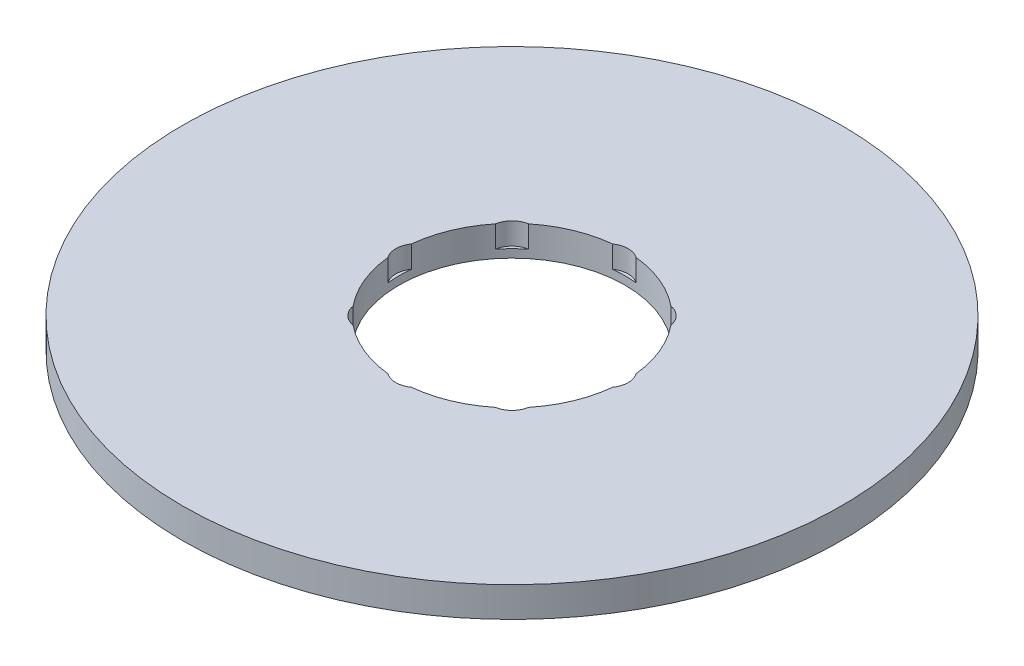
SolidWorks part; units mm, degrees
ref_plane "Front Plane" through (0, 0, 0) normal (0, 0, 1) x (1, 0, 0)
ref_plane "Top Plane" through (0, 0, 0) normal (0, 1, 0) x (1, 0, 0)
ref_plane "Right Plane" through (0, 0, 0) normal (1, 0, 0) x (0, 0, -1)
sketch "Sketch1" plane through (0, 0, 0) normal (0, 1, 0) x (1, 0, 0)
  circle A0 centre (0, 0) radius 87.5
  dimension "FLANGE_OD" = 175
extrude "Boss-Extrude1" add sketch "Sketch1" along normal blind 8
sketch "Sketch2" plane through (0, 0, 0) normal (0, 1, 0) x (1, 0, 0)
  circle A0 centre (0, 0) radius 30
  dimension "BORE_D" = 60
extrude "Cut-Extrude1" cut sketch "Sketch2" along normal through all
sketch "Sketch3" plane through (0, 8, 0) normal (0, 1, 0) x (1, 0, 0)
  circle A0 centre (0, 0) radius 25.4753 construction
  circle A1 centre (-25.4753, 0) radius 5.3567
  dimension "BOLT_D" = 10.7135
  dimension "BOLT_PCD" = 50.9506
extrude "Cut-Extrude2" cut sketch "Sketch3" against normal blind 5.8261
pattern_circular "CirPattern1" count 8 over 360 about axis through (0, 0, 0) along (0, 1, 0) of "Cut-Extrude2"
